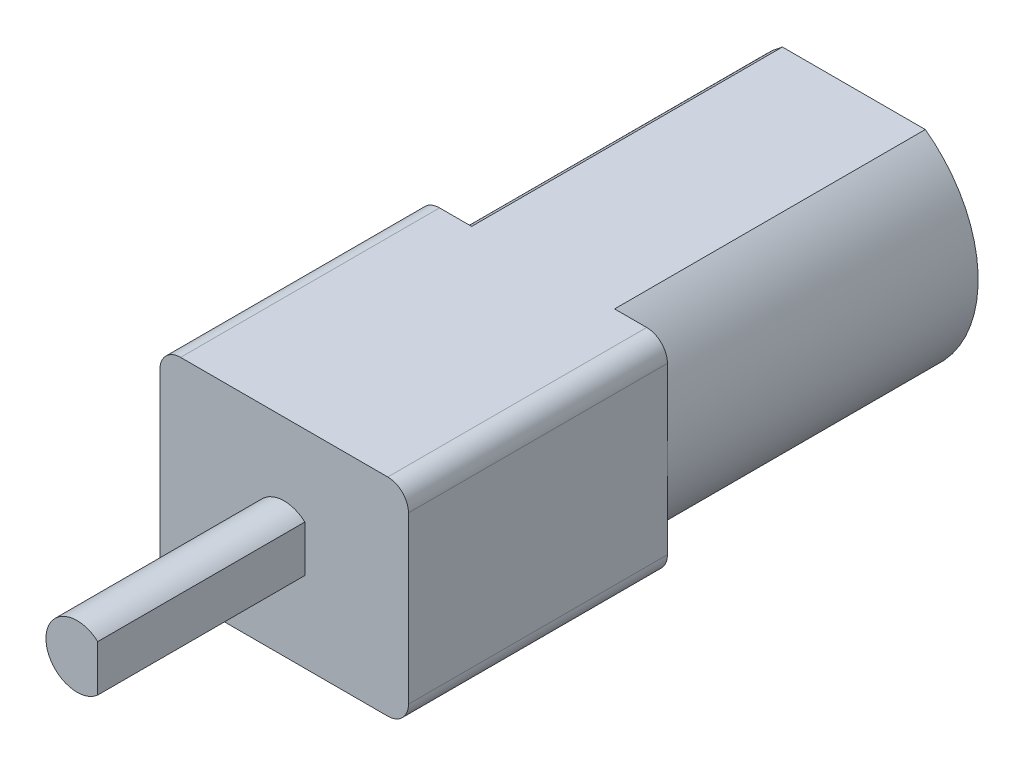
SolidWorks part; units mm, degrees
ref_plane "Front Plane" through (0, 0, 0) normal (0, 0, 1) x (1, 0, 0)
ref_plane "Top Plane" through (0, 0, 0) normal (0, 1, 0) x (1, 0, 0)
ref_plane "Right Plane" through (0, 0, 0) normal (1, 0, 0) x (0, 0, -1)
sketch "Sketch1" plane through (0, 0, 0) normal (0, 0, 1) x (1, 0, 0)
  line L1 (-3.45, 5) -> (3.45, 5)
  line L3 (-3.45, -5) -> (3.45, -5)
  line L5 (-6, 5) -> (6, -5) construction
  line L6 (-6, -5) -> (6, 5) construction
  line L11 (-3.45, 5) -> (3.45, -5) construction
  line L12 (-3.45, -5) -> (3.45, 5) construction
  arc A0 (-3.45, 5) -> (-3.45, -5) centre (0.177, 0) ccw
  arc A1 (3.45, 5) -> (3.45, -5) centre (-0.177, 0) cw
  point P0 (0, 0)
  point P6 (0, 0)
  dimension "D1" = 12
  dimension "D2" = 10
extrude "Boss-Extrude1" add sketch "Sketch1" along normal blind 15
sketch "Sketch2" plane through (0, 0, 15) normal (0, 0, 1) x (1, 0, 0)
  line L1 (-6, 5) -> (6, 5)
  line L2 (-6, 5) -> (-6, -5)
  line L3 (-6, -5) -> (6, -5)
  line L4 (6, 5) -> (6, -5)
  line L5 (-6, 5) -> (6, -5) construction
  line L6 (-6, -5) -> (6, 5) construction
  point P0 (0, 0)
  dimension "D1" = 10
  dimension "D2" = 12
extrude "Boss-Extrude2" add sketch "Sketch2" along normal blind 12.5
fillet "Fillet1" radius 1 4 edges at (6, 5, 21.25) (6, -5, 21.25) (-6, -5, 21.25) (-6, 5, 21.25)
sketch "Sketch3" plane through (0, 0, 27.5) normal (0, 0, 1) x (1, 0, 0)
  line L0 (1, 1.118) -> (1, -1.118)
  arc A0 (1, 1.118) -> (1, -1.118) centre (0, 0) ccw
  dimension "D1" = 1
  dimension "D2" = 3
extrude "Boss-Extrude3" add sketch "Sketch3" along normal blind 10
sketch "Sketch4" plane through (0, 0, 0) normal (0, 0, -1) x (-1, 0, 0)
  circle A0 centre (0, 0) radius 2.5
  dimension "D1" = 5
extrude "Boss-Extrude4" add sketch "Sketch4" along normal blind 1.2
